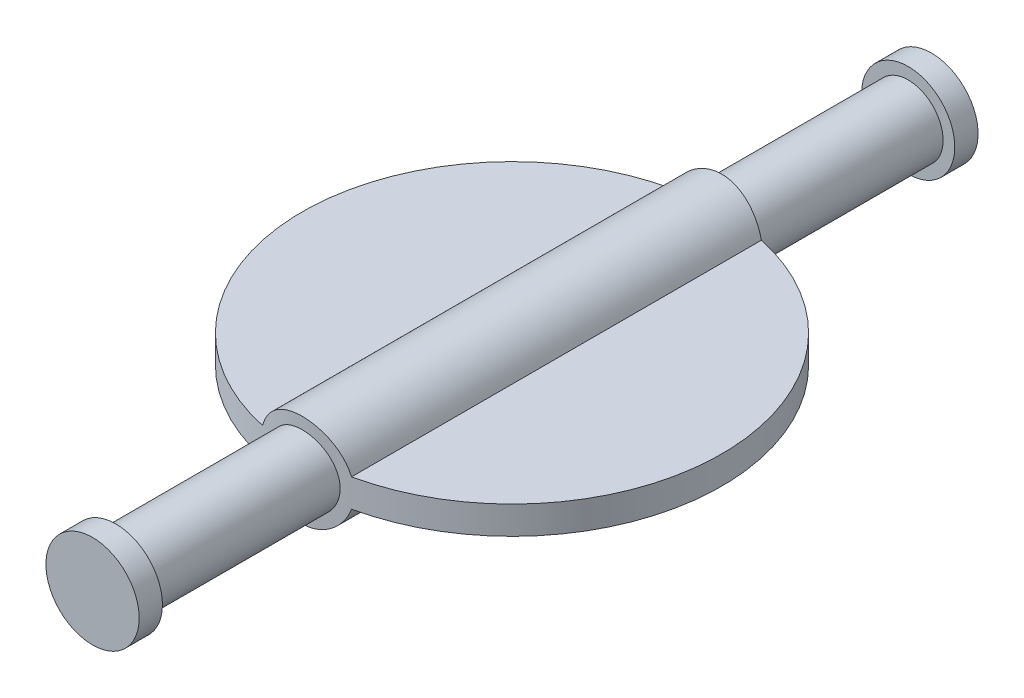
SolidWorks part; units mm, degrees
ref_plane "Front Plane" through (0, 0, 0) normal (0, 0, 1) x (1, 0, 0)
ref_plane "Top Plane" through (0, 0, 0) normal (0, 1, 0) x (1, 0, 0)
ref_plane "Right Plane" through (0, 0, 0) normal (1, 0, 0) x (0, 0, -1)
sketch "Sketch1" plane through (0, 0, 0) normal (0, 0, 1) x (1, 0, 0)
  circle A0 centre (0, 0) radius 1.5
  dimension "D1" = 3
extrude "Boss-Extrude1" add sketch "Sketch1" along normal blind 36
sketch "Sketch2" plane through (0, 0, 0) normal (0, 0, -1) x (-1, 0, 0)
  circle A0 centre (0, 0) radius 2
  dimension "D1" = 4
extrude "Boss-Extrude2" add sketch "Sketch2" against normal blind 1
sketch "Sketch3" plane through (0, 0, 36) normal (0, 0, 1) x (1, 0, 0)
  circle A0 centre (0, 0) radius 2
  dimension "D1" = 4
extrude "Boss-Extrude4" add sketch "Sketch3" against normal blind 1
ref_plane "Plane1" through (0, 0, 18) normal (0, 0, 1) x (1, 0, 0)
sketch "Sketch6" plane through (0, 0, 0) normal (0, 1, 0) x (1, 0, 0)
  line L0 (0, -36) -> (0, 0) construction
  line L1 (2, 0) -> (-2, 0) construction
  line L2 (-2, -36) -> (2, -36) construction
sketch "Sketch7" plane through (0, 0, 36) normal (0, 0, 1) x (1, 0, 0)
  line L0 (-3.2997, 0) -> (4.7055, 0) construction
ref_plane "Plane2" through (0, 0, 0) normal (0, -1, 0) x (-1, 0, 0)
sketch "Sketch8" plane through (0, 0, 0) normal (0, -1, 0) x (-1, 0, 0)
  line L0 (0, -36) -> (0, 0) construction
  circle A0 centre (0, -18) radius 9
  dimension "D1" = 18
extrude "Boss-Extrude6" add sketch "Sketch8" along normal blind 0.6 and the other way blind 0.6
sketch "Sketch4" plane through (0, 0, 18) normal (0, 0, 1) x (1, 0, 0)
  circle A0 centre (0, 0) radius 2
  dimension "D1" = 4
extrude "Boss-Extrude5" add sketch "Sketch4" along normal up to surface and the other way up to surface up to face at (5.2447, 0, 18) other way up to face at (5.2447, 0, 18)
